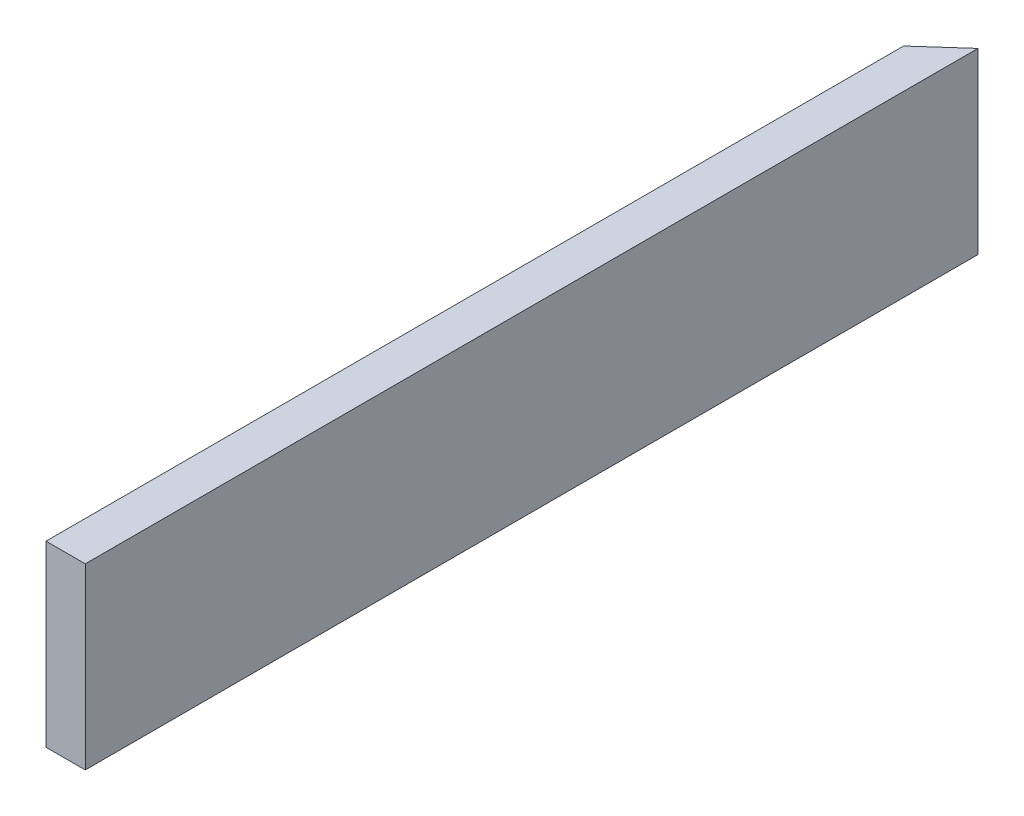
SolidWorks part; units mm, degrees
ref_plane "Front Plane" through (0, 0, 0) normal (0, 0, 1) x (1, 0, 0)
ref_plane "Top Plane" through (0, 0, 0) normal (0, 1, 0) x (1, 0, 0)
ref_plane "Right Plane" through (0, 0, 0) normal (1, 0, 0) x (0, 0, -1)
sketch "Sketch1" plane through (0, 0, 0) normal (0, 0, 1) x (1, 0, 0)
  line L1 (-3.1032, 12.8387) -> (-0.9032, 12.8387)
  line L2 (-3.1032, 12.8387) -> (-3.1032, 2.8387)
  line L3 (-3.1032, 2.8387) -> (-0.9032, 2.8387)
  line L4 (-0.9032, 12.8387) -> (-0.9032, 2.8387)
  dimension "D1" = 2.2
  dimension "D2" = 10
extrude "Boss-Extrude1" add sketch "Sketch1" along normal blind 50
ref_plane "Plane1" through (0, 12.8387, 0) normal (0, 1, 0) x (1, 0, 0)
sketch "Sketch3" plane through (0, 12.8387, 0) normal (0, 1, 0) x (1, 0, 0)
  line L0 (-0.9032, 0) -> (-3.1032, -1.967)
  line L1 (-3.1032, -50) -> (-3.1032, 0) construction
  line L2 (-3.1032, -1.967) -> (-3.1032, 0)
  line L3 (-3.1032, 0) -> (-0.9032, 0)
  dimension "D1" = 41.8
extrude "Cut-Extrude1" cut sketch "Sketch3" against normal blind 52
